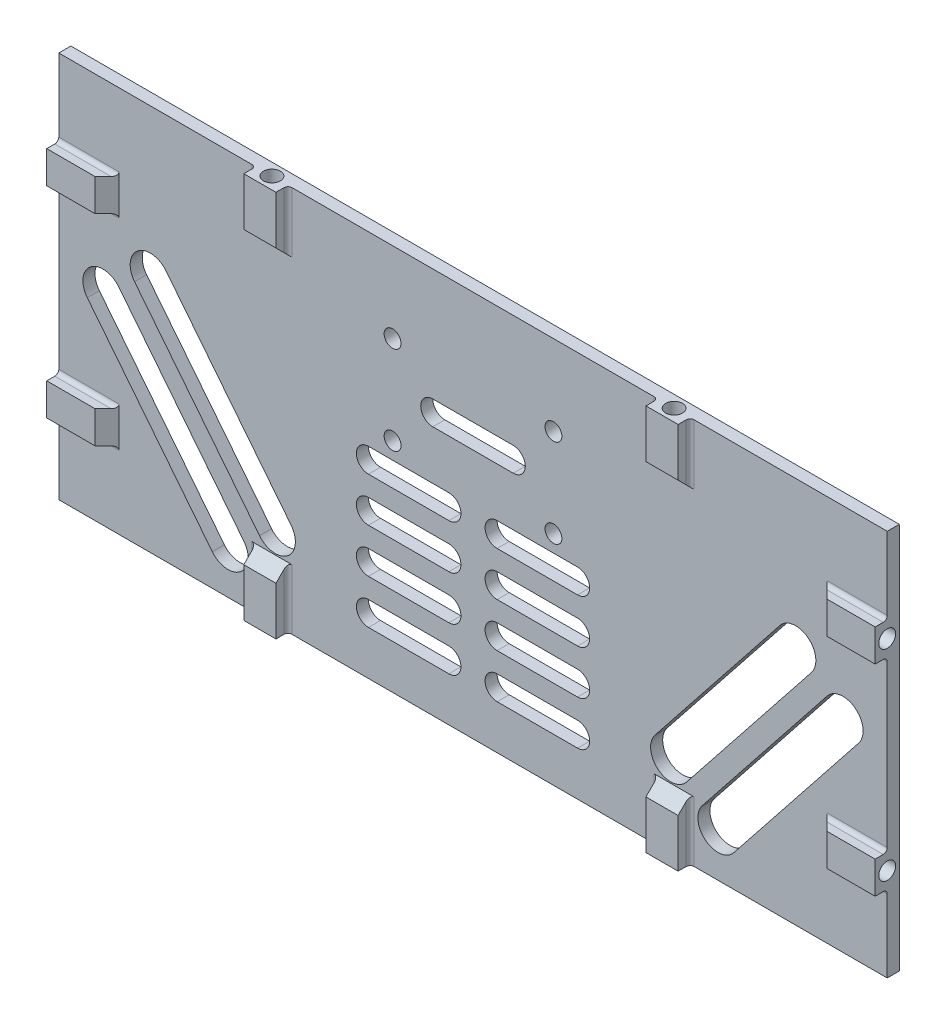
SolidWorks part; units mm, degrees
ref_plane "Front Plane" through (0, 0, 0) normal (1, 0, 0) x (0, 1, 0)
ref_plane "Top Plane" through (0, 0, 0) normal (0, 0, 1) x (0, 1, 0)
ref_plane "Right Plane" through (0, 0, 0) normal (0, 1, 0) x (-1, 0, 0)
sketch "Sketch1" plane through (0, 0, 0) normal (0, 0, 1) x (0, 1, 0)
  line L0 (11, 163.9146) -> (50.1625, 195) construction
  line L1 (0, 0) -> (96.2019, 0)
  line L2 (0, 0) -> (0, 206)
  line L3 (0, 206) -> (96.2019, 206)
  line L4 (96.2019, 0) -> (96.2019, 206)
  line L5 (7.8915, 167.8308) -> (47.0539, 198.9162)
  line L6 (14.1085, 159.9983) -> (53.271, 191.0838)
  line L7 (20.3256, 152.1659) -> (59.4881, 183.2513) construction
  line L8 (17.2171, 156.0821) -> (56.3795, 187.1675)
  line L9 (23.4342, 148.2496) -> (62.5966, 179.335)
  line L10 (20.3256, 53.8341) -> (59.4881, 22.7487) construction
  line L11 (23.4342, 57.7504) -> (62.5966, 26.665)
  line L12 (17.2171, 49.9179) -> (56.3795, 18.8325)
  line L13 (11, 42.0854) -> (50.1625, 11) construction
  line L14 (14.1085, 46.0017) -> (53.271, 14.9162)
  line L15 (7.8915, 38.1692) -> (47.0539, 7.0838)
  line L16 (6, 200) -> (90.2019, 200) construction
  line L17 (90.2019, 6) -> (90.2019, 200) construction
  line L18 (6, 6) -> (90.2019, 6) construction
  line L19 (6, 6) -> (6, 200) construction
  line L20 (55.8833, 147.5809) -> (78.9144, 118.5655) construction
  line L21 (65.5213, 70.5614) -> (46.6427, 46.7775) construction
  line L22 (96.2019, 103) -> (0, 103) construction
  line L23 (14, 129) -> (14, 109) construction
  line L24 (17, 129) -> (17, 109)
  line L25 (11, 129) -> (11, 109)
  line L26 (25, 129) -> (25, 109) construction
  line L27 (28, 129) -> (28, 109)
  line L28 (22, 129) -> (22, 109)
  line L29 (36, 129) -> (36, 109) construction
  line L30 (39, 129) -> (39, 109)
  line L31 (33, 129) -> (33, 109)
  line L32 (47, 129) -> (47, 109) construction
  line L33 (50, 129) -> (50, 109)
  line L34 (44, 129) -> (44, 109)
  line L41 (14, 77) -> (14, 97) construction
  line L42 (17, 77) -> (17, 97)
  line L43 (11, 77) -> (11, 97)
  line L44 (25, 77) -> (25, 97) construction
  line L45 (28, 77) -> (28, 97)
  line L46 (22, 77) -> (22, 97)
  line L47 (36, 77) -> (36, 97) construction
  line L48 (39, 77) -> (39, 97)
  line L49 (33, 77) -> (33, 97)
  line L50 (47, 77) -> (47, 97) construction
  line L51 (50, 77) -> (50, 97)
  line L52 (44, 77) -> (44, 97)
  line L53 (54.2019, 83) -> (76.2019, 83) construction
  line L56 (54.2019, 83) -> (54.2019, 123) construction
  line L59 (65.2019, 113) -> (65.2019, 93) construction
  line L60 (68.2019, 113) -> (68.2019, 93)
  line L61 (62.2019, 113) -> (62.2019, 93)
  line L67 (54.2019, 123) -> (76.2019, 123) construction
  line L68 (76.2019, 83) -> (76.2019, 123) construction
  line L69 (54.2019, 83) -> (76.2019, 123) construction
  line L70 (54.2019, 123) -> (76.2019, 83) construction
  line L95 (69, 129) -> (69, 109) construction
  line L96 (72, 129) -> (72, 109)
  line L97 (66, 129) -> (66, 109)
  line L98 (58, 129) -> (58, 109) construction
  line L99 (61, 129) -> (61, 109)
  line L100 (55, 129) -> (55, 109)
  line L101 (69, 129) -> (69, 109) construction
  line L102 (72, 129) -> (72, 109)
  line L103 (66, 129) -> (66, 109)
  line L104 (58, 129) -> (58, 109) construction
  line L105 (61, 129) -> (61, 109)
  line L106 (55, 129) -> (55, 109)
  arc A0 (7.8915, 167.8308) -> (14.1085, 159.9983) centre (11, 163.9146) ccw
  arc A1 (53.271, 191.0838) -> (47.0539, 198.9162) centre (50.1625, 195) ccw
  arc A2 (17.2171, 156.0821) -> (23.4342, 148.2496) centre (20.3256, 152.1659) ccw
  arc A3 (62.5966, 179.335) -> (56.3795, 187.1675) centre (59.4881, 183.2513) ccw
  arc A4 (23.4342, 57.7504) -> (17.2171, 49.9179) centre (20.3256, 53.8341) ccw
  arc A5 (56.3795, 18.8325) -> (62.5966, 26.665) centre (59.4881, 22.7487) ccw
  arc A6 (14.1085, 46.0017) -> (7.8915, 38.1692) centre (11, 42.0854) ccw
  arc A7 (47.0539, 7.0838) -> (53.271, 14.9162) centre (50.1625, 11) ccw
  circle A9 centre (76.2019, 123) radius 2.1
  circle A11 centre (76.2019, 83) radius 2.1
  arc A12 (17, 129) -> (11, 129) centre (14, 129) ccw
  arc A13 (11, 109) -> (17, 109) centre (14, 109) ccw
  arc A14 (28, 129) -> (22, 129) centre (25, 129) ccw
  arc A15 (22, 109) -> (28, 109) centre (25, 109) ccw
  arc A16 (39, 129) -> (33, 129) centre (36, 129) ccw
  arc A17 (33, 109) -> (39, 109) centre (36, 109) ccw
  arc A18 (50, 129) -> (44, 129) centre (47, 129) ccw
  arc A19 (44, 109) -> (50, 109) centre (47, 109) ccw
  arc A24 (17, 77) -> (11, 77) centre (14, 77) cw
  arc A25 (11, 97) -> (17, 97) centre (14, 97) cw
  arc A26 (28, 77) -> (22, 77) centre (25, 77) cw
  arc A27 (22, 97) -> (28, 97) centre (25, 97) cw
  arc A28 (39, 77) -> (33, 77) centre (36, 77) cw
  arc A29 (33, 97) -> (39, 97) centre (36, 97) cw
  arc A30 (50, 77) -> (44, 77) centre (47, 77) cw
  arc A31 (44, 97) -> (50, 97) centre (47, 97) cw
  arc A36 (68.2019, 113) -> (62.2019, 113) centre (65.2019, 113) ccw
  arc A37 (62.2019, 93) -> (68.2019, 93) centre (65.2019, 93) ccw
  circle A42 centre (54.2019, 123) radius 2.1
  circle A43 centre (54.2019, 83) radius 2.1
  arc A64 (72, 129) -> (66, 129) centre (69, 129) ccw
  arc A65 (66, 109) -> (72, 109) centre (69, 109) ccw
  arc A66 (61, 129) -> (55, 129) centre (58, 129) ccw
  arc A67 (55, 109) -> (61, 109) centre (58, 109) ccw
  point P7 (30.5812, 179.4573)
  point P12 (39.9068, 167.7086)
  point P19 (39.9068, 38.2914)
  point P26 (30.5812, 26.5427)
  point P40 (65.2019, 103)
  point P42 (65.2019, 103)
  point P54 (14, 119)
  point P59 (65.2019, 103)
  point P63 (25, 119)
  point P70 (36, 119)
  point P77 (47, 119)
  point P84 (69, 119)
  point P94 (91.2696, 103)
  point P97 (14, 87)
  point P104 (25, 87)
  point P111 (36, 87)
  point P118 (47, 87)
  point P146 (58, 119)
  point P153 (69, 119)
  point P160 (58, 119)
  point P167 (69, 119)
  point P174 (58, 119)
  point P181 (69, 119)
  point P188 (58, 119)
  point P195 (69, 119)
  point P202 (58, 119)
  point P209 (69, 119)
  point P216 (58, 119)
  point P223 (69, 119)
  point P230 (58, 119)
  dimension "D9" = 4.2
  dimension "D1" = 96.2019
  dimension "D2" = 206
  dimension "D4" = 5
  dimension "D5" = 5
  dimension "D6" = 103.118
  dimension "D7" = 10
  dimension "D8" = 50
  dimension "D10" = 20
  dimension "D11" = 20
  dimension "D14" = 5
  dimension "D15" = 5
  dimension "D16" = 6
  dimension "20" = 20
  dimension "D17" = 6
  dimension "D18" = 20
  dimension "D19" = 6
  dimension "D12" = 22
  dimension "D3" = 6
  dimension "D13" = 6
extrude "Boss-Extrude1" add sketch "Sketch1" along normal blind 3
sketch "Sketch2" plane through (0, 0, 0) normal (0, -1, 0) x (1, 0, 0)
  line L0 (-153, 6) -> (-153, 0) construction
  line L1 (-157, 6) -> (-149, 6)
  line L2 (-53, 6) -> (-53, 0) construction
  line L5 (-103, 3) -> (-103, 0) construction
  line L6 (-206, 3) -> (0, 3) construction
  line L7 (-206, 0) -> (0, 0) construction
  line L8 (-157, 6) -> (-157, 0)
  line L9 (-157, 0) -> (-149, 0)
  line L10 (-149, 6) -> (-149, 0)
  line L11 (-57, 6) -> (-57, 0)
  line L12 (-49, 0) -> (-57, 0)
  line L13 (-49, 6) -> (-49, 0)
  line L14 (-49, 6) -> (-57, 6)
  circle A0 centre (-153, 3) radius 2.1
  circle A2 centre (-53, 3) radius 2.1
  dimension "D3" = 6
  dimension "D1" = 4.2
  dimension "D4" = 8
  dimension "D2" = 50
extrude "Boss-Extrude2" add sketch "Sketch2<3>" against normal blind 12 contours L8 L9 L10 L1 | L14 L11 L12 L13
sketch "Sketch2<3>" plane through (0, 0, 0) normal (0, -1, 0) x (1, 0, 0) same geometry as "Sketch2"
extrude "Boss-Extrude3" add sketch "Sketch2<4>" along normal blind 12 from surface contours L14 L11 L12 L13 | L1 L10 L9 L8 starting at face at (-103, 96.2019, 1.5)
sketch "Sketch2<4>" plane through (0, 0, 0) normal (0, -1, 0) x (1, 0, 0) same geometry as "Sketch2"
sketch "Sketch3" plane through (0, 0, 0) normal (1, 0, 0) x (0, 1, 0)
  line L1 (23.1009, 6) -> (23.1009, 0) construction
  line L4 (0, 3) -> (96.2019, 3) construction
  line L5 (48.1009, 3) -> (48.1009, 0) construction
  line L6 (0, 0) -> (96.2019, 0) construction
  line L7 (19.1009, 0) -> (27.1009, 0)
  line L8 (19.1009, 0) -> (19.1009, 6)
  line L9 (19.1009, 6) -> (27.1009, 6)
  line L10 (27.1009, 0) -> (27.1009, 6)
  line L11 (77.1009, 0) -> (69.1009, 0)
  line L12 (69.1009, 0) -> (69.1009, 6)
  line L13 (77.1009, 6) -> (69.1009, 6)
  line L14 (77.1009, 0) -> (77.1009, 6)
  circle A0 centre (23.1009, 3) radius 2.1
  circle A2 centre (73.1009, 3) radius 2.1
  dimension "D3" = 6
  dimension "D1" = 4.2
  dimension "D4" = 8
  dimension "D2" = 25
extrude "Boss-Extrude4" add sketch "Sketch3<3>" against normal blind 12 contours L9 L10 L7 L8 | L13 L12 L11 L14
sketch "Sketch3<3>" plane through (0, 0, 0) normal (1, 0, 0) x (0, 1, 0) same geometry as "Sketch3"
extrude "Boss-Extrude5" add sketch "Sketch3<4>" along normal blind 12 from surface contours L9 L10 L7 L8 | L13 L12 L11 L14 starting at face at (-206, 48.1009, 1.5)
sketch "Sketch3<4>" plane through (0, 0, 0) normal (1, 0, 0) x (0, 1, 0) same geometry as "Sketch3"
extrude "Cut-Extrude1" cut sketch "Sketch2" against normal blind 10 contours A2 | A0
extrude "Cut-Extrude2" cut sketch "Sketch2<2>" along normal blind 10 from surface contours A2 | A0 starting at face at (-103, 96.2019, 3.5)
sketch "Sketch2<2>" plane through (0, 0, 0) normal (0, -1, 0) x (1, 0, 0) same geometry as "Sketch2"
extrude "Cut-Extrude3" cut sketch "Sketch3" against normal blind 10 contours A2 | A0
extrude "Cut-Extrude4" cut sketch "Sketch3<2>" along normal blind 10 from surface contours A2 | A0 starting at face at (-206, 48.1009, 3.5)
sketch "Sketch3<2>" plane through (0, 0, 0) normal (1, 0, 0) x (0, 1, 0) same geometry as "Sketch3"
chamfer "Chamfer1" distance 3 angle 45 8 edges at (-53, 84.2019, 3) (-153, 84.2019, 3) (-194, 73.1009, 3) (-194, 23.1009, 3) (-153, 12, 3) (-53, 12, 3) (-12, 23.1009, 3) (-12, 73.1009, 3)
fillet "Fillet1" radius 1 16 edges at (-149, 7.5, 3) (-157, 7.5, 3) (-198.5, 27.1009, 3) (-198.5, 19.1009, 3) (-198.5, 69.1009, 3) (-198.5, 77.1009, 3) (-157, 88.7019, 3) (-149, 88.7019, 3) (-7.5, 69.1009, 3) (-49, 88.7019, 3) (-57, 88.7019, 3) (-7.5, 77.1009, 3) (-57, 7.5, 3) (-49, 7.5, 3) (-7.5, 27.1009, 3) (-7.5, 19.1009, 3)
equation "\"MotorDriverLength\"= 60mm"
equation "\"MotorLength\"= 60"
equation "\"MotorDriverWidth\"=44"
equation "\"MotorWidth\"= 37"
equation "\"InnerWallThickness\"=3"
equation "\"BatteryWidth\"= 60"
equation "\"OuterWallThickness\" = 6"
equation "\"CompartmentHeight\"=37"
equation "\"CompartmentWidth\"= \"MotorDriverLength\""
equation "\"MotorDiameter\"=37"
equation "\"BatteryHeight\"=24.2019"
equation "\"MotorDriverHeight\"=28"
equation "\"CircuitHeight\"=30"
equation "\"FanThickness\"= 10"
equation "\"FanHeight\"=50"
equation "\"MotorShaftHole\"=12"
equation "\"BearingBore\"=4"
equation "\"MinShinWidth\"= 20"
equation "\"ShinThickness\"=10"
equation "\"PivotDistance\"=30"
equation "\"ThighLength\"= 200"
equation "\"KneeLength\" =20"
equation "\"HipBore\"=27"
equation "\"ThighThickness\"=20"
equation "\"MaxBending\"=135"
equation "\"MaxStretchingAngle\"= 140"
equation "\"ThighJointDistance\"=157.485"
equation "\"ShinLength\"=120"
equation "\"BearingDiameter\"= 10"
equation "\"CircuitLength\"=50"
equation "\"ChessisInnerWidth\"= \"OuterWallThickness\" * 2 + \"MotorDriverLength\" + \"MotorDiameter\" + \"InnerWallThickness\" * 3 + \"CircuitLength\""
equation "\"ChessisHeight\"= \"BatteryHeight\" + 10 + \"InnerWallThickness\" + \"MotorDiameter\" + 10 + \"OuterWallThickness\" * 2"
equation "\"D1@Sketch1\"=\"ChessisHeight\""
equation "\"ChassisWidth\"= \"MotorDriverWidth\"*4+30"
equation "\"D2@Sketch1\"=\"ChassisWidth\""
equation "\"D1@Boss-Extrude1\"=\"OuterWallThickness\""
equation "\"D3@Sketch2\"=\"OuterWallThickness\""
equation "\"D3@Sketch3\"=\"OuterWallThickness\""
